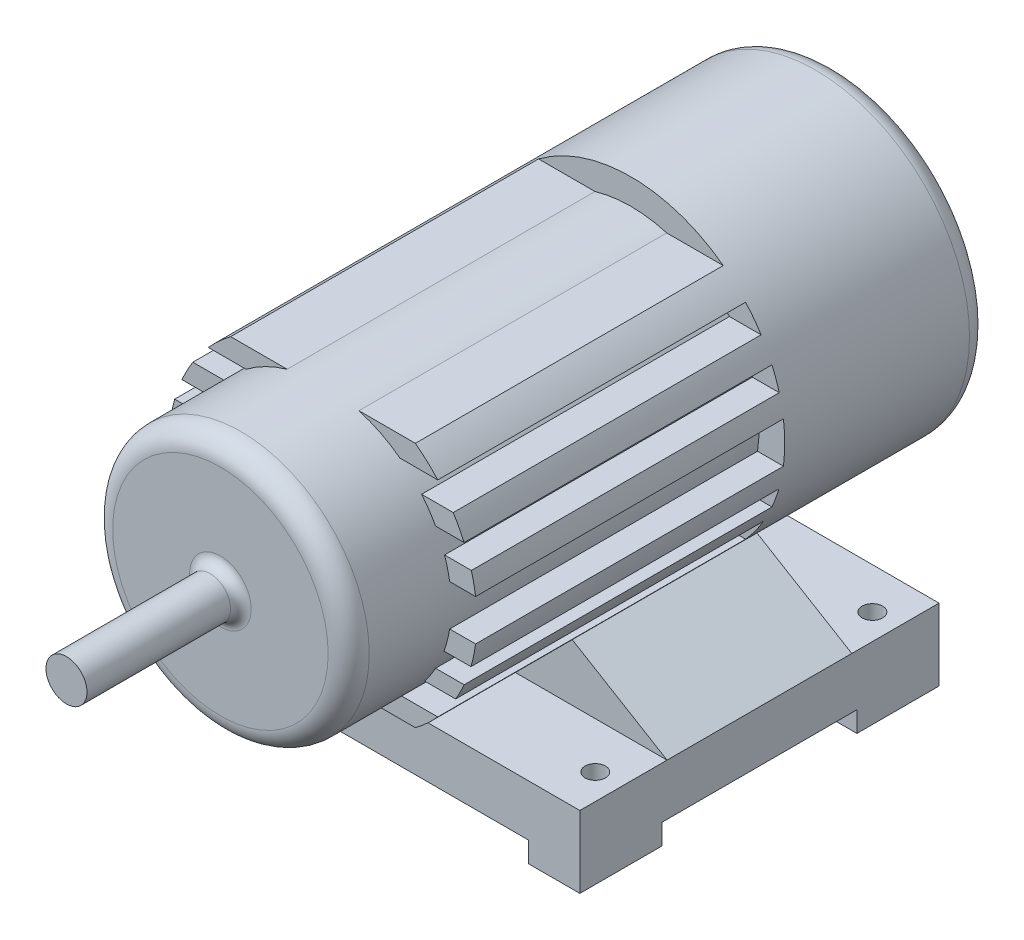
SolidWorks part; units mm, degrees
ref_plane "Front Plane" through (0, 0, 0) normal (0, 0, 1) x (1, 0, 0)
ref_plane "Top Plane" through (0, 0, 0) normal (0, 1, 0) x (1, 0, 0)
ref_plane "Right Plane" through (0, 0, 0) normal (1, 0, 0) x (0, 0, -1)
sketch "Sketch1" plane through (0, 0, 0) normal (0, 0, 1) x (1, 0, 0)
  circle A0 centre (0, 0) radius 150
  dimension "D1" = 300
extrude "Boss-Extrude1" add sketch "Sketch1" along normal blind 200
sketch "Sketch7" plane through (0, 0, 200) normal (0, 0, 1) x (1, 0, 0)
  line L0 (0, 0) -> (0, 100) construction
  line L1 (-90, 120) -> (90, 120)
  line L3 (-111.8034, 100) -> (111.8034, 100)
  line L4 (-126.8858, 80) -> (126.8858, 80)
  line L5 (-137.4773, 60) -> (137.4773, 60)
  line L6 (144.1634, -41.4356) -> (-144.1634, -41.4356)
  line L7 (111.8034, -100) -> (-111.8034, -100)
  line L8 (148.6607, -20) -> (-148.6607, -20)
  line L9 (90, -120) -> (-90, -120)
  line L10 (144.5683, 40) -> (-144.5683, 40)
  line L11 (148.6607, 20) -> (-148.6607, 20)
  line L12 (137.4773, -60) -> (-137.4773, -60)
  line L13 (129.2326, -76.1507) -> (-129.2326, -76.1507)
  arc A0 (-90, 120) -> (-111.8034, 100) centre (0, 0) ccw
  circle A1 centre (0, 0) radius 150 construction
  arc A2 (111.8034, 100) -> (90, 120) centre (0, 0) ccw
  arc A3 (-126.8858, 80) -> (-137.4773, 60) centre (0, 0) ccw
  arc A4 (137.4773, 60) -> (126.8858, 80) centre (0, 0) ccw
  arc A5 (-144.5683, 40) -> (-148.6607, 20) centre (0, 0) ccw
  arc A6 (148.6607, 20) -> (144.5683, 40) centre (0, 0) ccw
  arc A7 (-148.6607, -20) -> (-144.1634, -41.4356) centre (0, 0) ccw
  arc A8 (90, -120) -> (111.8034, -100) centre (0, 0) ccw
  arc A9 (129.2326, -76.1507) -> (137.4773, -60) centre (0, 0) ccw
  arc A10 (-111.8034, -100) -> (-90, -120) centre (0, 0) ccw
  arc A11 (-137.4773, -60) -> (-129.2326, -76.1507) centre (0, 0) ccw
  arc A12 (144.1634, -41.4356) -> (148.6607, -20) centre (0, 0) ccw
  dimension "D1" = 20
  dimension "D2" = 100
  dimension "D3" = 20
  dimension "D4" = 20
  dimension "D5" = 21.4356
  dimension "D6" = 20
  dimension "D7" = 16.1507
  dimension "D8" = 100
  dimension "D9" = 60
  dimension "D10" = 20
  dimension "D11" = 60
  dimension "D12" = 20
extrude "Boss-Extrude11" add sketch "Sketch7" along normal blind 300
sketch "Sketch12" plane through (0, 0, 500) normal (0, 0, 1) x (1, 0, 0)
  circle A0 centre (0, 0) radius 125
  dimension "D1" = 250
extrude "Boss-Extrude14" add sketch "Sketch12" along normal blind 400 from surface separate body starting at face at (0, 0, 200)
ref_plane "Plane4" through (0, -210, 0) normal (0, -1, 0) x (-1, 0, 0)
sketch "Sketch13" plane through (0, -210, 0) normal (0, -1, 0) x (-1, 0, 0)
  line L0 (0, -449.7357) -> (0, 0) construction
  line L1 (-200, -99.7357) -> (200, -99.7357)
  line L2 (-200, -99.7357) -> (-200, -449.7357)
  line L3 (-200, -449.7357) -> (200, -449.7357)
  line L4 (200, -99.7357) -> (200, -449.7357)
  line L5 (150, 0) -> (-150, 0) construction
  line L6 (200, -274.7357) -> (-200, -274.7357) construction
  line L7 (200, -179.7357) -> (150, -179.7357)
  line L8 (-150, -99.7357) -> (-150, -179.7357)
  line L9 (-150, -179.7357) -> (-200, -179.7357)
  line L10 (150, -179.7357) -> (150, -99.7357)
  line L20 (-150, -369.7357) -> (-200, -369.7357)
  line L21 (-150, -449.7357) -> (-150, -369.7357)
  line L25 (200, -369.7357) -> (150, -369.7357)
  line L26 (150, -369.7357) -> (150, -449.7357)
  circle A8 centre (-175, -139.7357) radius 10
  circle A9 centre (175, -139.7357) radius 10
  circle A10 centre (175, -409.7357) radius 10
  circle A11 centre (-175, -409.7357) radius 10
  point P24 (0, 0)
  point P28 (-175, -139.7357)
  dimension "D7" = 20
  dimension "D9" = 40
  dimension "D1" = 99.7357
  dimension "D2" = 350
  dimension "D3" = 400
  dimension "D4" = 80
  dimension "D5" = 50
  dimension "D6" = 50
  dimension "D8" = 25
extrude "Boss-Extrude15" add sketch "Sketch13" against normal blind 50 separate body contours L26 L25 L4 L7 L10 L1 L8 L9 L2 L20 L21 L3 | L9 L8 L1 L2 | L3 L21 L20 L2 | L25 L26 L3 L4 | L10 L7 L4 L1 region at (175, -210, 100.6791) region at (0, -210, 274.7357) region at (-175, -210, 100.6791) region at (175, -210, 370.6791) region at (-199.0566, -210, 409.7357)
cosmetic thread "Cosmetic Thread1" parameters "D2"=22
cosmetic thread "Cosmetic Thread2" parameters "D2"=22
cosmetic thread "Cosmetic Thread3" parameters "D2"=22
cosmetic thread "Cosmetic Thread4" parameters "D2"=22
extrude "Boss-Extrude16" add sketch "Sketch13<3>" along normal blind 20 contours L3 L21 L20 L2 | L9 L8 L1 L2 | L25 L26 L3 L4 | L10 L7 L4 L1 region at (175, -210, 100.6791) region at (-175, -210, 100.6791) region at (175, -210, 370.6791) region at (-199.0566, -210, 409.7357)
sketch "Sketch13<3>" plane through (0, -210, 0) normal (0, -1, 0) x (-1, 0, 0) same geometry as "Sketch13"
ref_plane "Plane5" through (0, 0, 274.7357) normal (0, 0, 1) x (1, 0, 0)
sketch "Sketch14" plane through (0, 0, 274.7357) normal (0, 0, 1) x (1, 0, 0)
  line L0 (-200, -160) -> (200, -160)
  line L1 (200, -160) -> (100, -100)
  line L2 (100, -100) -> (-100, -100)
  line L3 (-100, -100) -> (-200, -160)
  line L4 (200, -160) -> (-200, -160) construction
  dimension "D1" = 60
  dimension "D2" = 200
extrude "Boss-Extrude17" add sketch "Sketch14" along normal mid plane 180
sketch "Sketch16" plane through (0, 0, 600) normal (0, 0, 1) x (1, 0, 0)
  circle A0 centre (0, 0) radius 20
  dimension "D1" = 40
extrude "Boss-Extrude18" add sketch "Sketch16" along normal blind 150
fillet "Fillet2" radius 10 1 edges at (20, 0, 600)
fillet "Fillet3" radius 20 2 edges at (150, 0, 0) (125, 0, 600)
